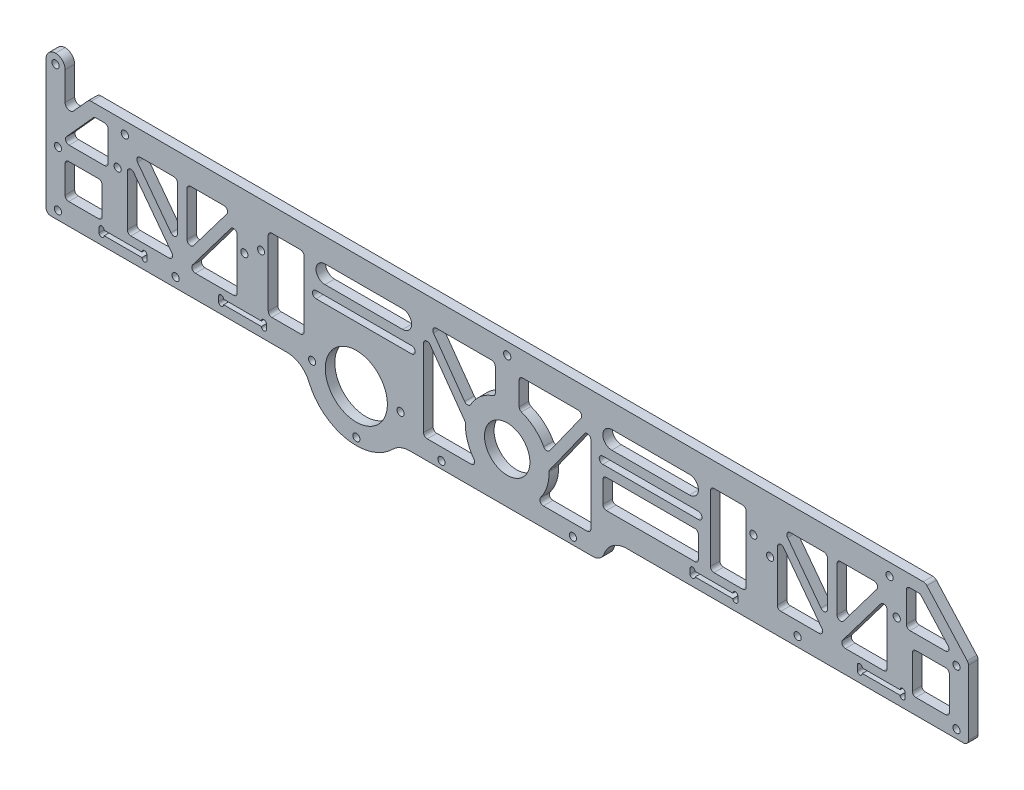
SolidWorks part; units mm, degrees
material "Thornel Mat VMA"
ref_plane "前视基准面" through (0, 0, 0) normal (0, 0, 1) x (1, 0, 0)
ref_plane "上视基准面" through (0, 0, 0) normal (0, 1, 0) x (1, 0, 0)
ref_plane "右视基准面" through (0, 0, 0) normal (1, 0, 0) x (0, 0, -1)
sketch "草图1" plane through (0, 0, 0) normal (0, 0, 1) x (1, 0, 0)
  line L1 (-193, -25) -> (193, -25)
  line L2 (-193, -25) -> (-193, 25)
  line L3 (-193, 25) -> (193, 25)
  line L4 (193, -25) -> (193, 25)
  line L5 (-193, -25) -> (193, 25) construction
  line L6 (-193, 25) -> (193, -25) construction
  point P0 (0, 0)
  dimension "D1" = 386
  dimension "D2" = 50
extrude "凸台-拉伸1" add sketch "草图1" along normal blind 4
sketch "草图2" plane through (0, 0, 0) normal (0, 0, -1) x (-1, 0, 0)
  circle A0 centre (160, 20) radius 1.25 construction
  circle A1 centre (0, 20) radius 1.25 construction
  circle A2 centre (-160, 20) radius 1.25 construction
  circle A3 centre (160, 20) radius 1.25 construction
  circle A4 centre (0, 20) radius 1.25 construction
  circle A5 centre (-160, 20) radius 1.25 construction
  circle A6 centre (-160, 20) radius 1.525
  circle A7 centre (0, 20) radius 1.525
  circle A8 centre (160, 20) radius 1.525
  dimension "D1" = 3.05
extrude "切除-拉伸1" cut sketch "草图2" against normal blind 33
sketch "草图3" plane through (0, 0, 0) normal (0, 0, -1) x (-1, 0, 0)
  line L0 (0, 0) -> (0, 25) construction
  line L1 (-193, 25) -> (193, 25) construction
  line L2 (-163, 6.5) -> (-103, 6.5) construction
  circle A0 centre (-163, 6.5) radius 1.5 construction
  circle A2 centre (-103, 6.5) radius 1.5
  circle A3 centre (-163, 6.5) radius 1.5
  circle A4 centre (163, 6.5) radius 1.5
  circle A5 centre (103, 6.5) radius 1.5
  dimension "D1" = 60
  dimension "D2" = 3
extrude "切除-拉伸2" cut sketch "草图3" against normal mid plane 10
sketch "草图4" plane through (0, 0, 0) normal (0, 0, -1) x (-1, 0, 0)
  line L0 (193, -25) -> (-193, -25) construction
  line L1 (-40, -35) -> (40, -35)
  line L2 (-40, -35) -> (-40, -15)
  line L3 (-40, -15) -> (40, -15)
  line L4 (40, -35) -> (40, -15)
  line L5 (-40, -35) -> (40, -15) construction
  line L6 (-40, -15) -> (40, -35) construction
  point P0 (0, -25)
  dimension "D1" = 10
  dimension "D2" = 80
extrude "凸台-拉伸3" add sketch "草图4" against normal up to surface (4 mm away) up to face at (161.5, 6.5, 4)
fillet "圆角1" radius 10 2 edges at (-40, -25, 2) (40, -25, 2)
fillet "圆角2" radius 5 2 edges at (-40, -35, 2) (40, -35, 2)
sketch "草图5" plane through (0, 0, 0) normal (0, 0, -1) x (-1, 0, 0)
  line L0 (-35.8579, -35) -> (35.8579, -35) construction
  line L1 (0, 0) -> (0, -14) construction
  circle A0 centre (0, -14) radius 9.5
  dimension "D2" = 19
  dimension "D1" = 21
extrude "切除-拉伸3" cut sketch "草图5" against normal blind 40
sketch "草图6" plane through (0, 0, 4) normal (0, 0, 1) x (1, 0, 0)
  line L0 (-35.8579, -35) -> (-80.8579, -35)
  line L1 (-80.8579, -35) -> (-80.8579, -25)
  line L2 (-193, -25) -> (-50, -25) construction
  line L3 (-80.8579, -25) -> (-35.8579, -25)
  line L4 (-35.8579, -25) -> (-35.8579, -35)
  dimension "D1" = 45
extrude "凸台-拉伸4" add sketch "草图6" against normal up to surface (4 mm away) up to face at (-9.5, -14, 0)
sketch "草图7" plane through (0, 0, 4) normal (0, 0, 1) x (1, 0, 0)
  circle A0 centre (-63.1397, -22.8) radius 6.5 construction
  circle A1 centre (-63.1397, -22.8) radius 6.5 construction
  circle A2 centre (-63.1397, -22.8) radius 6.55
  dimension "D1" = 13.1
extrude "切除-拉伸4" cut sketch "草图7" against normal blind 10
sketch "草图8" plane through (0, 0, 4) normal (0, 0, 1) x (1, 0, 0)
  circle A0 centre (-63.1397, -22.8) radius 21.5122
  circle A1 centre (-63.1397, -22.8) radius 6.55 construction
  circle A2 centre (-63.1397, -22.8) radius 6.55
extrude "凸台-拉伸5" add sketch "草图8" against normal up to surface (4 mm away) up to face at (-69.6897, -22.8, 0)
sketch "草图10" plane through (0, 0, 4) normal (0, 0, 1) x (1, 0, 0)
  circle A0 centre (-63.1397, -22.8) radius 13
  dimension "D1" = 26
extrude "切除-拉伸5" cut sketch "草图10" against normal blind 21
sketch "草图11" plane through (0, 0, 4) normal (0, 0, 1) x (1, 0, 0)
  line L0 (-80, 2) -> (-40, 2) construction
  line L1 (-80, 3.5) -> (-40, 3.5)
  line L2 (-80, 0.5) -> (-40, 0.5)
  line L4 (193, 25) -> (-193, 25) construction
  line L5 (0, 0) -> (0, 25) construction
  line L6 (80, 2) -> (40, 2) construction
  line L7 (80, 3.5) -> (40, 3.5)
  line L8 (80, 0.5) -> (40, 0.5)
  arc A0 (-80, 3.5) -> (-80, 0.5) centre (-80, 2) ccw
  arc A1 (-40, 0.5) -> (-40, 3.5) centre (-40, 2) ccw
  arc A2 (80, 3.5) -> (80, 0.5) centre (80, 2) cw
  arc A3 (40, 0.5) -> (40, 3.5) centre (40, 2) cw
  point P2 (-60, 2)
  point P14 (60, 2)
  dimension "D1" = 1.5
  dimension "D2" = 40
  dimension "D3" = 23
  dimension "D4" = 40
extrude "切除-拉伸6" cut sketch "草图11" against normal blind 10
sketch "草图12" plane through (0, 0, 0) normal (0, 0, -1) x (-1, 0, 0)
  line L0 (-110, 2) -> (-80, 2) construction
  line L1 (0, 0) -> (0, 25) construction
  line L2 (-193, 25) -> (193, 25) construction
  circle A0 centre (-110, 2) radius 1.5
  circle A1 centre (110, 2) radius 1.5
  dimension "D2" = 3
  dimension "D1" = 30
extrude "切除-拉伸7" cut sketch "草图12" against normal blind 10
sketch "草图13" plane through (0, 0, 4) normal (0, 0, 1) x (1, 0, 0)
  line L0 (-175, 25) -> (-193, 5)
  line L1 (193, 25) -> (-193, 25) construction
  line L3 (-193, 25) -> (-193, -25) construction
  line L4 (-193, 5) -> (-193, 25)
  line L5 (-193, 25) -> (-175, 25)
  line L6 (0, 0) -> (0, 25) construction
  line L7 (193, 25) -> (175, 25)
  line L8 (193, 5) -> (193, 25)
  line L9 (175, 25) -> (193, 5)
  dimension "D1" = 18
  dimension "D2" = 20
extrude "切除-拉伸8" cut sketch "草图13" against normal blind 10
sketch "草图15" plane through (0, 0, 4) normal (0, 0, 1) x (1, 0, 0)
  line L0 (-138.7695, -25) -> (-138.7695, -21) construction
  line L1 (-193, -25) -> (-84.5391, -25) construction
  circle A0 centre (-138.7695, -21) radius 1.5
  dimension "D2" = 3
  dimension "D1" = 4
extrude "切除-拉伸9" cut sketch "草图15" against normal blind 10
sketch "草图16" plane through (0, 0, 4) normal (0, 0, 1) x (1, 0, 0)
  line L0 (193, -21) -> (121.5, -21) construction
  line L1 (193, -25) -> (193, 5) construction
  line L2 (121.5, -21) -> (50, -21) construction
  line L3 (50, -21) -> (50, -25) construction
  line L4 (50, -25) -> (193, -25) construction
  circle A2 centre (121.5, -21) radius 1.5
  dimension "D2" = 3
  dimension "D1" = 4
extrude "切除-拉伸10" cut sketch "草图16" against normal blind 10
sketch "草图17" plane through (0, 0, 4) normal (0, 0, 1) x (1, 0, 0)
  line L0 (-45.4215, -35) -> (35.8579, -35) construction
  line L1 (-27.5, 4) -> (27.5, 4) construction
  line L2 (-27.5, 4) -> (-27.5, -32) construction
  line L3 (-27.5, -32) -> (27.5, -32) construction
  line L4 (27.5, 4) -> (27.5, -32) construction
  line L5 (-27.5, 4) -> (27.5, -32) construction
  line L6 (-27.5, -32) -> (27.5, 4) construction
  circle A0 centre (27.5, -32) radius 1.5
  circle A1 centre (-27.5, -32) radius 1.5
  point P0 (0, -14)
  dimension "D3" = 3
  dimension "D1" = 3
  dimension "D2" = 55
extrude "切除-拉伸11" cut sketch "草图17" against normal blind 10
sketch "草图18" plane through (0, 0, 4) normal (0, 0, 1) x (1, 0, 0)
  circle A0 centre (-63.1397, -22.8) radius 18.5122 construction
  arc A1 (-84.5391, -25) -> (-45.4215, -35) centre (-63.1397, -22.8) ccw construction
  circle A2 centre (-63.1397, -41.3122) radius 1.5
  circle A3 centre (-44.6275, -22.8) radius 1.5
  circle A4 centre (-81.6519, -22.8) radius 1.5
  dimension "D1" = 3
  dimension "D2" = 3
extrude "切除-拉伸12" cut sketch "草图18" against normal blind 10
fillet "圆角3" radius 10 2 edges at (-84.5391, -25, 2) (-45.4215, -35, 2)
sketch "草图19" [suppressed] plane through (0, 0, 4) normal (0, 0, 1) x (1, 0, 0)
  circle A0 centre (-63.1397, -22.8) radius 9.5 construction
  circle A1 centre (-63.1397, -13.3) radius 1.5
  circle A2 centre (-54.9125, -18.05) radius 1.5
  circle A3 centre (-54.9125, -27.55) radius 1.5
  circle A4 centre (-63.1397, -32.3) radius 1.5
  circle A5 centre (-71.3669, -27.55) radius 1.5
  circle A6 centre (-71.3669, -18.05) radius 1.5
  point P17 (-63.1397, -22.8)
  dimension "D1" = 19
  dimension "D2" = 3
  dimension "D3" = 6
extrude "切除-拉伸13" [suppressed] cut sketch "草图19" against normal blind 50
fillet "圆角4" radius 2 6 edges at (193, -25, 2) (193, 5, 2) (175, 25, 2) (-175, 25, 2) (-193, 5, 2) (-193, -25, 2)
sketch "草图20" plane through (0, 0, 4) normal (0, 0, 1) x (1, 0, 0)
  line L0 (0, 0) -> (0, 25) construction
  line L1 (174.1093, 25) -> (-174.1093, 25) construction
  circle A0 centre (-188, -21.5) radius 1.5 construction
  circle A1 centre (-188, 1.5) radius 1.5 construction
  circle A2 centre (-188, -21.5) radius 1.5
  circle A3 centre (-188, 1.5) radius 1.5
  circle A4 centre (188, 1.5) radius 1.5
  circle A5 centre (188, -21.5) radius 1.5
extrude "切除-拉伸14" cut sketch "草图20" against normal blind 50
sketch "草图21" plane through (0, 0, 4) normal (0, 0, 1) x (1, 0, 0)
  line L0 (-191, -25) -> (-92.1944, -25) construction
  line L1 (-170.7695, -21) -> (-150.7695, -21)
  line L2 (-170.7695, -21) -> (-170.7695, -19)
  line L3 (-170.7695, -19) -> (-150.7695, -19)
  line L4 (-150.7695, -21) -> (-150.7695, -19)
  line L5 (-170.7695, -21) -> (-150.7695, -19) construction
  line L6 (-170.7695, -19) -> (-150.7695, -21) construction
  line L7 (50, -25) -> (191, -25) construction
  line L8 (-120.7695, -21) -> (-100.7695, -21)
  line L9 (-120.7695, -21) -> (-120.7695, -19)
  line L10 (-120.7695, -19) -> (-100.7695, -19)
  line L11 (-100.7695, -21) -> (-100.7695, -19)
  line L12 (-120.7695, -21) -> (-100.7695, -19) construction
  line L13 (-120.7695, -19) -> (-100.7695, -21) construction
  line L14 (76.5, -21) -> (96.5, -21)
  line L15 (76.5, -21) -> (76.5, -19)
  line L16 (76.5, -19) -> (96.5, -19)
  line L17 (96.5, -21) -> (96.5, -19)
  line L18 (76.5, -21) -> (96.5, -19) construction
  line L19 (76.5, -19) -> (96.5, -21) construction
  line L20 (121.5, -21) -> (121.5, -14.5833) construction
  line L21 (166.5, -19) -> (146.5, -19)
  line L22 (146.5, -21) -> (146.5, -19)
  line L23 (166.5, -21) -> (146.5, -21)
  line L24 (166.5, -21) -> (166.5, -19)
  circle A0 centre (-138.7695, -21) radius 1.5 construction
  circle A1 centre (121.5, -21) radius 1.5 construction
  point P0 (-160.7695, -20)
  point P5 (86.5, -20)
  point P11 (-110.7695, -20)
  dimension "D8" = 18
  dimension "D1" = 2
  dimension "D2" = 4
  dimension "D3" = 20
  dimension "D4" = 22
  dimension "D5" = 2
  dimension "D6" = 4
  dimension "D7" = 20
  dimension "D9" = 20
  dimension "D10" = 2
  dimension "D11" = 4
  dimension "D12" = 25
extrude "切除-拉伸15" cut sketch "草图21" against normal blind 10
sketch "草图22" plane through (0, 0, 4) normal (0, 0, 1) x (1, 0, 0)
  line L0 (-170.7695, -21) -> (-150.7695, -21) construction
  line L1 (-150.7695, -19) -> (-170.7695, -19) construction
  line L2 (-100.7695, -19) -> (-120.7695, -19) construction
  line L3 (-120.7695, -21) -> (-100.7695, -21) construction
  circle A0 centre (-151.8195, -21) radius 1.05
  circle A1 centre (-151.8195, -19) radius 1.05
  circle A2 centre (-169.7195, -19) radius 1.05
  circle A3 centre (-169.7195, -21) radius 1.05
  circle A4 centre (-119.7195, -19) radius 1.05
  circle A5 centre (-119.7195, -21) radius 1.05
  circle A6 centre (-101.8195, -19) radius 1.05
  circle A7 centre (-101.8195, -21) radius 1.05
  dimension "D1" = 2.1
extrude "切除-拉伸16" cut sketch "草图22" against normal blind 10 contours A0 A1 | A2 A3 | A3 A2 | A1 A0 | A5 A4 | A4 A5 | A7 A6 | A6 A7 region at (-151.8195, -21.0125, 4) region at (-151.8195, -18.9875, 4) region at (-169.7195, -18.9875, 4) region at (-169.7195, -21.0125, 4) region at (-119.7195, -18.9875, 4) region at (-119.7195, -21.0125, 4) region at (-101.8195, -18.9875, 4) region at (-101.8195, -21.0125, 4)
sketch "草图23" plane through (0, 0, 4) normal (0, 0, 1) x (1, 0, 0)
  line L0 (76.5, -21) -> (96.5, -21) construction
  line L1 (96.5, -19) -> (76.5, -19) construction
  line L2 (166.5, -19) -> (146.5, -19) construction
  line L3 (146.5, -21) -> (166.5, -21) construction
  circle A0 centre (77.55, -21) radius 1.05
  circle A1 centre (77.55, -19) radius 1.05
  circle A2 centre (95.45, -19) radius 1.05
  circle A3 centre (95.45, -21) radius 1.05
  circle A4 centre (147.55, -19) radius 1.05
  circle A5 centre (147.55, -21) radius 1.05
  circle A6 centre (165.45, -19) radius 1.05
  circle A7 centre (165.45, -21) radius 1.05
  dimension "D1" = 2.1
extrude "切除-拉伸17" cut sketch "草图23" against normal blind 10 contours A0 A1 | A1 A0 | A3 A2 | A4 A5 | A7 A6 | A6 A7 | A2 A3 | A4 region at (77.55, -21.0125, 4) region at (77.55, -18.9875, 4) region at (95.45, -18.9875, 4) region at (95.45, -21.0125, 4) region at (147.55, -21.0125, 4) region at (165.45, -18.9875, 4) region at (165.45, -21.0125, 4)
sketch "草图24" plane through (0, 0, 0) normal (0, 0, -1) x (-1, 0, 0)
  line L0 (-172.7732, 20) -> (-186.7232, 4.5)
  line L1 (-186.7232, 4.5) -> (-167, 4.5)
  line L2 (-167, 4.5) -> (-167, 20)
  line L3 (-167, 20) -> (-172.7732, 20)
  line L4 (-185, -1.5) -> (-169.5, -1.5)
  line L5 (-169.5, -1.5) -> (-169.5, -18.5)
  line L6 (-169.5, -18.5) -> (-185, -18.5)
  line L7 (-185, -18.5) -> (-185, -1.5)
  line L8 (-159, 15) -> (-113, 15)
  line L9 (-113, 15) -> (-113, -15.5)
  line L10 (-113, -15.5) -> (-159, -15.5)
  line L11 (-159, -15.5) -> (-159, 15)
  line L12 (-174.1093, 25) -> (174.1093, 25) construction
  line L13 (-100, 15) -> (-100, -15.5)
  line L14 (-100, -15.5) -> (-85, -15.5)
  line L15 (-85, -15.5) -> (-85, 15)
  line L16 (-85, 15) -> (-100, 15)
  line L17 (-76.25, 11.25) -> (-43.75, 11.25) construction
  line L18 (-76.25, 15) -> (-43.75, 15)
  line L19 (-76.25, 7.5) -> (-43.75, 7.5)
  line L20 (-80, -3.5) -> (-80, -15.5)
  line L21 (-80, -15.5) -> (-40, -15.5)
  line L22 (-40, -15.5) -> (-40, -3.5)
  line L23 (-40, -3.5) -> (-80, -3.5)
  line L24 (-35, 15) -> (-35, -27)
  line L25 (-35, -27) -> (-11.7154, -27)
  line L26 (-35, 15) -> (-5, 15)
  line L27 (-5, 15) -> (-5, 2.7705)
  line L28 (-192.4866, 5.5705) -> (-175.5959, 24.3379) construction
  line L29 (-166.5, -19) -> (-166.5, -21) construction
  line L30 (-80, 0.5) -> (-40, 0.5) construction
  line L31 (-40, 3.5) -> (-80, 3.5) construction
  line L32 (-80, 11.25) -> (-80, -3.5) construction
  line L39 (-40, 11.25) -> (-40, -3.5) construction
  line L40 (0, 0) -> (0, 57.9851) construction
  line L41 (5, 15) -> (5, 2.7705)
  line L42 (35, 15) -> (5, 15)
  line L43 (35, 15) -> (35, -27)
  line L44 (35, -27) -> (11.7154, -27)
  line L45 (76.25, 11.25) -> (43.75, 11.25) construction
  line L46 (76.25, 15) -> (43.75, 15)
  line L47 (76.25, 7.5) -> (43.75, 7.5)
  line L48 (85, -15.5) -> (85, 15)
  line L49 (100, -15.5) -> (85, -15.5)
  line L50 (100, 15) -> (100, -15.5)
  line L51 (85, 15) -> (100, 15)
  line L52 (167, 20) -> (172.7732, 20)
  line L53 (167, 4.5) -> (167, 20)
  line L54 (186.7232, 4.5) -> (167, 4.5)
  line L55 (172.7732, 20) -> (186.7232, 4.5)
  line L56 (169.5, -18.5) -> (185, -18.5)
  line L57 (169.5, -1.5) -> (169.5, -18.5)
  line L58 (185, -1.5) -> (169.5, -1.5)
  line L59 (185, -18.5) -> (185, -1.5)
  line L60 (113, -15.5) -> (159, -15.5)
  line L61 (113, 15) -> (113, -15.5)
  line L62 (159, 15) -> (113, 15)
  line L63 (159, -15.5) -> (159, 15)
  arc A0 (-76.25, 15) -> (-76.25, 7.5) centre (-76.25, 11.25) ccw
  arc A1 (-43.75, 7.5) -> (-43.75, 15) centre (-43.75, 11.25) ccw
  circle A4 centre (0, -14) radius 17.5
  arc A5 (-5, 2.7705) -> (-11.7154, -27) centre (0, -14) ccw
  circle A6 centre (0, 20) radius 1.525 construction
  circle A7 centre (-188, 1.5) radius 1.5 construction
  circle A8 centre (-163, 6.5) radius 1.5 construction
  circle A9 centre (-188, -21.5) radius 1.5 construction
  arc A10 (-146.5, -19) -> (-148.6, -19) centre (-147.55, -19) ccw construction
  circle A11 centre (-110, 2) radius 1.5 construction
  circle A12 centre (-103, 6.5) radius 1.5 construction
  arc A13 (-80, 3.5) -> (-80, 0.5) centre (-80, 2) ccw construction
  arc A14 (-40, 0.5) -> (-40, 3.5) centre (-40, 2) ccw construction
  circle A15 centre (-27.5, -32) radius 1.5 construction
  arc A16 (5, 2.7705) -> (11.7154, -27) centre (0, -14) cw
  arc A17 (76.25, 15) -> (76.25, 7.5) centre (76.25, 11.25) cw
  arc A18 (43.75, 7.5) -> (43.75, 15) centre (43.75, 11.25) cw
  point P20 (-60, 11.25)
  point P80 (60, 11.25)
  dimension "D12" = 4
  dimension "D15" = 3
  dimension "D1" = 10
  dimension "D3" = 5
  dimension "D4" = 5
  dimension "D5" = 5
  dimension "D6" = 3
  dimension "D7" = 4
  dimension "D8" = 3
  dimension "D9" = 3
  dimension "D10" = 3
  dimension "D11" = 3
  dimension "D13" = 3.5
  dimension "D14" = 3
  dimension "D16" = 5
  dimension "D17" = 5
  dimension "D18" = 4
  dimension "D19" = 4
  dimension "D20" = 5
  dimension "D21" = 5
  dimension "D22" = 5
  dimension "D2" = 8
extrude "切除-拉伸18" cut sketch "草图24" against normal blind 10
sketch "草图25" plane through (0, 0, 0) normal (0, 0, -1) x (-1, 0, 0)
  line L0 (-136, 15) -> (-136, -15.5) construction
  line L1 (-113, 15) -> (-159, 15) construction
  line L2 (-159, -15.5) -> (-113, -15.5) construction
  line L3 (-159, 15) -> (-136, -15.5) construction
  line L4 (-136, -15.5) -> (-113, 15) construction
  line L5 (-157.4031, 16.2042) -> (-134.4031, -14.2958)
  line L6 (-137.5969, -14.2958) -> (-114.5969, 16.2042)
  line L7 (-134, 15) -> (-134, -15.5)
  line L8 (-160.5969, 13.7958) -> (-137.5969, -16.7042)
  line L9 (-134.4031, -16.7042) -> (-111.4031, 13.7958)
  line L10 (-138, 15) -> (-138, -15.5)
  line L11 (-157.4031, 16.2042) -> (-160.5969, 13.7958)
  line L12 (-134.4031, -14.2958) -> (-137.5969, -16.7042)
  line L13 (-137.5969, -14.2958) -> (-134.4031, -16.7042)
  line L14 (-114.5969, 16.2042) -> (-111.4031, 13.7958)
  line L15 (-134, 15) -> (-138, 15)
  line L16 (-134, -15.5) -> (-138, -15.5)
  dimension "D1" = 2
  dimension "D2" = 2
extrude "凸台-拉伸6" add sketch "草图25" against normal up to surface (4 mm away) contours L12 L16 L10 L5 L11 L8 | L7 L15 L10 L5 L6 | L7 L16 L13 L9 L14 L6 | L16 L7 L6 L5 L12 | L16 L13 L6 L5 L10 | L6 L13 L12 L5 region at (148.4132, 0.8576, 0) region at (136, 2.0626, 0) region at (137.3198, -12.7624, 0) region at (134.6802, -12.7624, 0) region at (136, -13.9914, 0) region at (123.5868, 0.8576, 0) up to face at (-92.5, -0.25, 4)
mirror "镜向1" about plane through (0, 0, 0) normal (1, 0, 0) of "凸台-拉伸6"
sketch "草图26" plane through (0, 0, 0) normal (0, 0, -1) x (-1, 0, 0)
  line L0 (-35, 15) -> (-17.0711, -10.1493) construction
  line L1 (-35, 15) -> (-32.5438, 15)
  line L2 (-5, 15) -> (-35, 15) construction
  line L3 (-32.5438, 15) -> (-16.3387, -7.7312)
  line L4 (-35, 11.5546) -> (-17.4731, -13.0306)
  line L5 (-35, 15) -> (-35, -27) construction
  line L6 (-35, 15) -> (-35, 11.5546)
  arc A0 (-5, 2.7705) -> (-11.7154, -27) centre (0, -14) ccw construction
  arc A2 (-16.3387, -7.7312) -> (-17.4731, -13.0306) centre (0, -14) ccw
  dimension "D1" = 2
extrude "凸台-拉伸7" add sketch "草图26" against normal up to surface (4 mm away) up to face at (-152.1683, -6.4406, 4)
mirror "镜向2" about plane through (0, 0, 0) normal (1, 0, 0) of "凸台-拉伸7"
fillet "圆角5" radius 1.5 67 edges at (-32.5438, 15, 2) (-16.3387, -7.7312, 2) (-17.4731, -13.0306, 2) (-35, 11.5546, 2) (35, 11.5546, 2) (17.4731, -13.0306, 2) (16.3387, -7.7312, 2) (32.5438, 15, 2) (-138, -9.5261, 2) (-138, 15, 2) (-134, 15, 2) (-134, -9.5261, 2) (-113, 11.6782, 2) (-159, 11.6782, 2) (113, 11.6782, 2) (-113, -15.5, 2) (-159, -15.5, 2) (-185, -18.5, 2) (-185, -1.5, 2) (-169.5, -1.5, 2) (-167, 4.5, 2) (-186.7232, 4.5, 2) (-172.7732, 20, 2) (-167, 20, 2) (-100, -15.5, 2) (-100, 15, 2) (-85, 15, 2) (-85, -15.5, 2) (-11.7154, -27, 2) (-35, -27, 2) (-5, 15, 2) (-5, 2.7705, 2) (35, -27, 2) (11.7154, -27, 2) (5, 2.7705, 2) (5, 15, 2) (80, -3.5, 2) (80, -15.5, 2) (40, -15.5, 2) (40, -3.5, 2) (100, 15, 2) (100, -15.5, 2) (85, -15.5, 2) (85, 15, 2) (113, -15.5, 2) (-133.4951, -15.5, 2) (-138.5049, -15.5, 2) (-115.5049, 15, 2) (-156.4951, 15, 2) (133.4951, -15.5, 2) (134, 15, 2) (115.5049, 15, 2) (134, -9.5261, 2) (138, 15, 2) (156.4951, 15, 2) (138, -9.5261, 2) (138.5049, -15.5, 2) (159, 11.6782, 2) (159, -15.5, 2) (186.7232, 4.5, 2) (172.7732, 20, 2) (167, 20, 2) (167, 4.5, 2) (185, -1.5, 2) (169.5, -1.5, 2) (185, -18.5, 2) (169.5, -18.5, 2)
sketch "草图27" plane through (0, 0, 0) normal (0, 0, -1) x (-1, 0, 0)
  line L0 (185, -18.5) -> (170.6428, -18.5)
  line L1 (169.5, -17.9732) -> (169.5, -16)
  line L2 (169.5, -16) -> (185, -16)
  line L3 (169.5, -3) -> (169.5, -17.9732) construction
  line L4 (185, -17) -> (185, -3) construction
  line L5 (185, -16) -> (185, -18.5)
  line L6 (170.6428, -18.5) -> (183.5, -18.5) construction
  arc A0 (169.5, -17.9732) -> (168.6695, -19) centre (169.7195, -19) ccw construction
  arc A1 (170.6428, -18.5) -> (169.5, -17.9732) centre (169.7195, -19) ccw
  dimension "D2" = 2.1
  dimension "D1" = 3
extrude "凸台-拉伸8" add sketch "草图27" against normal up to surface (4 mm away) up to face at (-25.1065, -14.4492, 4)
fillet "圆角6" radius 1.5 2 edges at (-185, -16, 2) (-169.5, -16, 2)
sketch "草图28" plane through (0, 0, 0) normal (0, 0, -1) x (-1, 0, 0)
  line L0 (193, 4.2325) -> (193, 35)
  line L1 (193, 35) -> (185, 35)
  line L2 (185, 35) -> (185, 13.8889)
  line L3 (175.5959, 24.3379) -> (192.4866, 5.5705) construction
  line L4 (185, 13.8889) -> (193, 4.2325)
  line L5 (-174.1093, 25) -> (174.1093, 25) construction
  dimension "D1" = 10
  dimension "D2" = 8
extrude "凸台-拉伸9" add sketch "草图28" against normal up to surface (4 mm away) up to face at (-177.25, -8.75, 4)
sketch "草图29" plane through (0, 0, 4) normal (0, 0, 1) x (1, 0, 0)
  line L0 (-185, 13.8889) -> (-185, 35) construction
  line L1 (-185, 35) -> (-193, 35) construction
  circle A0 centre (-189, 31) radius 1.5
  dimension "D3" = 3
  dimension "D1" = 4
  dimension "D2" = 4
extrude "切除-拉伸19" cut sketch "草图29" against normal blind 10
fillet "圆角7" radius 4 2 edges at (-185, 35, 2) (-193, 35, 2)
fillet "圆角8" radius 2 1 edges at (-185, 13.8889, 2)
sketch "草图30" [suppressed] plane through (0, 0, 4) normal (0, 0, 1) x (1, 0, 0)
  line L0 (193, 4.2325) -> (193, 35)
  line L1 (193, 35) -> (185, 35)
  line L2 (185, 35) -> (185, 13.8889)
  line L3 (175.5959, 24.3379) -> (192.4866, 5.5705) construction
  line L4 (185, 13.8889) -> (193, 4.2325)
  line L5 (174.1093, 25) -> (-174.1093, 25) construction
  dimension "D1" = 10
  dimension "D2" = 8
extrude "凸台-拉伸10" [suppressed] add sketch "草图30" against normal up to surface (4 mm away)
sketch "草图31" [suppressed] plane through (0, 0, 0) normal (0, 0, -1) x (-1, 0, 0)
  line L0 (-189, 35) -> (-189, 31) construction
  line L1 (-193, 35) -> (-185, 35) construction
  circle A0 centre (-189, 31) radius 1.5
  dimension "D1" = 3
  dimension "D2" = 4
extrude "切除-拉伸20" [suppressed] cut sketch "草图31" against normal blind 10
fillet "圆角9" [suppressed] radius 4
fillet "圆角10" [suppressed] radius 2
